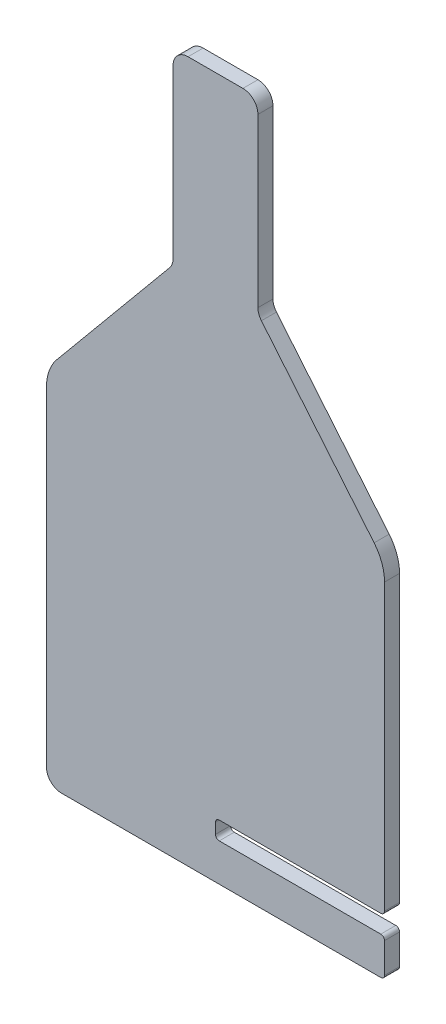
SolidWorks part; units mm, degrees
ref_plane "Alzado" through (0, 0, 0) normal (0, 0, 1) x (1, 0, 0)
ref_plane "Planta" through (0, 0, 0) normal (0, 1, 0) x (1, 0, 0)
ref_plane "Vista lateral" through (0, 0, 0) normal (1, 0, 0) x (0, 0, -1)
sketch "Croquis1" plane through (0, 0, 0) normal (0, 0, 1) x (1, 0, 0)
  line L0 (-5.65, 20) -> (-22.5, -0.3233)
  line L1 (-5.65, 45) -> (5.65, 45)
  line L2 (-22.5, -0.3233) -> (-22.5, -48.3233)
  line L3 (-22.5, -48.3233) -> (22.5, -48.3233)
  line L4 (22.5, -0.3233) -> (22.5, -48.3233)
  line L5 (-5.65, 45) -> (5.65, 45)
  line L6 (-5.65, 45) -> (-5.65, 20)
  line L8 (5.65, 45) -> (5.65, 19.9991)
  line L9 (5.65, 19.9991) -> (22.5, -0.3233)
  line L10 (0, 75.1867) -> (0, -77.6145) construction
  dimension "D1" = 45
  dimension "D2" = 25
  dimension "D3" = 5.65
  dimension "D4" = 22.5
  dimension "D5" = 45
  dimension "D6" = 5.65
  dimension "D7" = 26.3993
  dimension "D8" = 26.4
  dimension "D9" = 48
  dimension "D10" = 48
extrude "Saliente-Extruir1" add sketch "Croquis1" along normal blind 2 contours L6 L0 L2 L3 L4 L9 L8 L1
sketch "Croquis3" plane through (0, 0, 2) normal (0, 0, 1) x (1, 0, 0)
  line L0 (22.5, -0.3233) -> (22.5, -48.3233) construction
  line L1 (22.5, -40.9233) -> (0, -40.9233)
  line L2 (22.5, -40.9233) -> (22.5, -43.3233)
  line L3 (22.5, -43.3233) -> (0, -43.3233)
  line L4 (0, -40.9233) -> (0, -43.3233)
  line L5 (-22.5, -48.3233) -> (22.5, -48.3233) construction
  dimension "D1" = 2.4
  dimension "D2" = 5
  dimension "D3" = 22.5
extrude "Cortar-Extruir2" cut sketch "Croquis3" against normal up to surface (2 mm away) up to face at (0, 4.0882, 0)
fillet "Redondeo1" radius 2 5 edges at (-22.5, -48.3233, 1) (-5.65, 20, 1) (-5.65, 45, 1) (5.65, 19.9991, 1) (5.65, 45, 1)
fillet "Redondeo2" radius 6 2 edges at (-22.5, -0.3233, 1) (22.5, -0.3233, 1)
fillet "Redondeo3" radius 0.5 5 edges at (0, -40.9233, 1) (0, -43.3233, 1) (22.5, -48.3233, 1) (22.5, -43.3233, 1) (22.5, -40.9233, 1)
